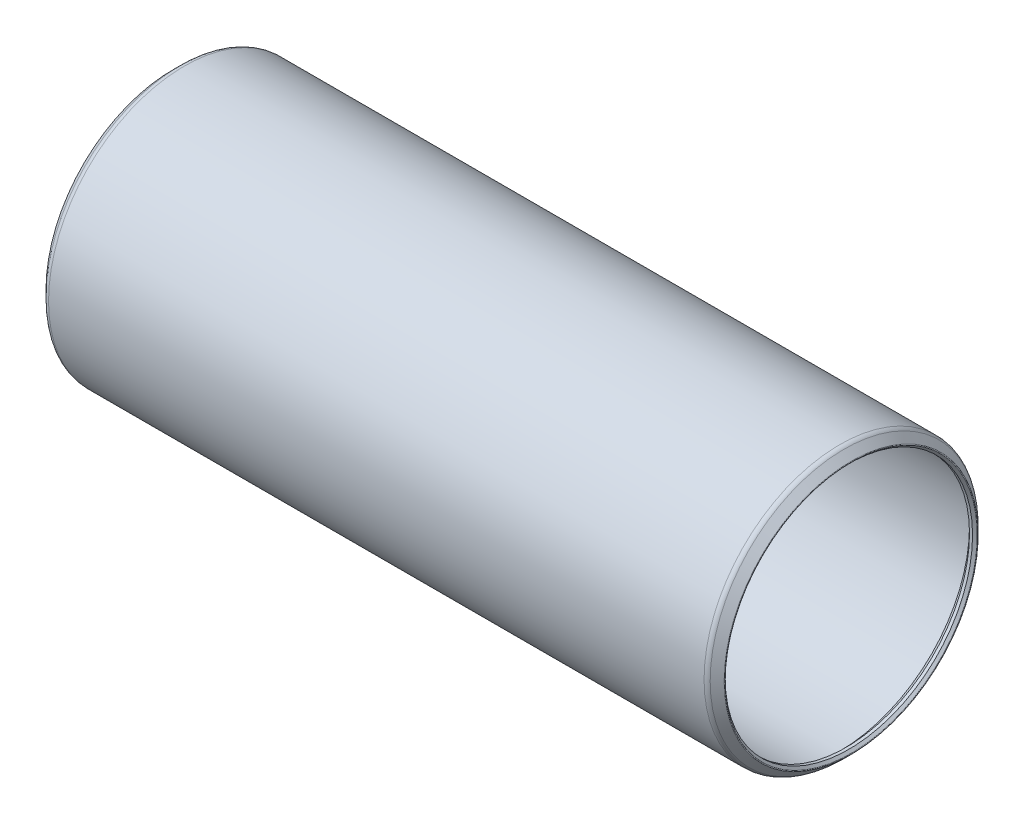
SolidWorks part; units mm, degrees
material "Cast Alloy Steel"
ref_plane "Front Plane" through (0, 0, 0) normal (0, 0, 1) x (1, 0, 0)
ref_plane "Top Plane" through (0, 0, 0) normal (0, 1, 0) x (1, 0, 0)
ref_plane "Right Plane" through (0, 0, 0) normal (1, 0, 0) x (0, 0, -1)
ref_plane "Plane1" through (115.1509, 0, 0) normal (1, 0, 0) x (0, 0, -1)
sketch "Sketch1" plane through (0, 0, 0) normal (0, 0, 1) x (1, 0, 0)
  line L0 (-0.9191, 21.7344) -> (-0.5271, 21.3423)
  line L1 (-0.5271, 21.3423) -> (0, 21.3423)
  line L2 (0, 21.3423) -> (1.0541, 22.3965)
  line L3 (1.0541, 22.3965) -> (114.0968, 22.3965)
  line L4 (114.0968, 22.3965) -> (115.1509, 21.3423)
  line L5 (115.1509, 21.3423) -> (115.6779, 21.3423)
  line L6 (115.6779, 21.3423) -> (116.07, 21.7344)
  line L7 (116.07, 21.914) -> (114.8676, 23.1164)
  line L8 (114.1222, 23.4251) -> (1.0287, 23.4251)
  line L9 (0.2833, 23.1164) -> (-0.9191, 21.914)
  line L10 (115.1509, 0) -> (0, 0) construction
  arc A0 (-0.9191, 21.914) -> (-0.9191, 21.7344) centre (-0.8293, 21.8242) ccw
  arc A1 (116.07, 21.7344) -> (116.07, 21.914) centre (115.9802, 21.8242) ccw
  arc A2 (114.8676, 23.1164) -> (114.1222, 23.4251) centre (114.1222, 22.3711) ccw
  arc A3 (1.0287, 23.4251) -> (0.2833, 23.1164) centre (1.0287, 22.371) ccw
revolve "Revolve1" add sketch "Sketch1" angle 360 about L10 reverse direction yes
ref_plane "Plane2" through (57.5755, 0, 0) normal (1, 0, 0) x (0, 0, -1)
ref_plane "cp1 XY" through (57.5755, 0, 0) normal (1, 0, 0) x (0, 0, -1)
ref_plane "cp1 XZ" through (0, 23.4251, 0) normal (0, -1, 0) x (-1, 0, 0)
ref_plane "cp1 YZ" through (0, 0, 0) normal (0, 0, -1) x (-1, 0, 0)
ref_axis "cp1 X" through (57.5755, 23.4251, 80.9) along (0, 0, -1)
ref_axis "cp1 Y" through (57.5755, -50, 0) along (0, 1, 0)
ref_axis "cp1 Z" through (80.9, 23.4251, 0) along (-1, 0, 0)
sketch3d "cp1"
  point P0 (57.5755, 23.4251, 0)
ref_plane "cp2 XY" through (57.5755, 0, 0) normal (1, 0, 0) x (0, 0, -1)
ref_plane "cp2 XZ" through (0, 0, 0) normal (0, -1, 0) x (-1, 0, 0)
ref_plane "cp2 YZ" through (0, 0, -23.4251) normal (0, 0, -1) x (-1, 0, 0)
ref_axis "cp2 X" through (57.5755, 0, 80.9) along (0, 0, -1)
ref_axis "cp2 Y" through (57.5755, -50, -23.4251) along (0, 1, 0)
ref_axis "cp2 Z" through (80.9, 0, -23.4251) along (-1, 0, 0)
sketch3d "cp2"
  point P0 (57.5755, 0, -23.4251)
ref_plane "cp3 XY" through (57.5755, 0, 0) normal (1, 0, 0) x (0, 0, -1)
ref_plane "cp3 XZ" through (0, -23.4251, 0) normal (0, -1, 0) x (-1, 0, 0)
ref_plane "cp3 YZ" through (0, 0, 0) normal (0, 0, -1) x (-1, 0, 0)
ref_axis "cp3 X" through (57.5755, -23.4251, 80.9) along (0, 0, -1)
ref_axis "cp3 Y" through (57.5755, -50, 0) along (0, 1, 0)
ref_axis "cp3 Z" through (80.9, -23.4251, 0) along (-1, 0, 0)
sketch3d "cp3"
  point P0 (57.5755, -23.4251, 0)
ref_plane "cp4 XY" through (57.5755, 0, 0) normal (1, 0, 0) x (0, 0, -1)
ref_plane "cp4 XZ" through (0, 0, 0) normal (0, -1, 0) x (-1, 0, 0)
ref_plane "cp4 YZ" through (0, 0, 23.4251) normal (0, 0, -1) x (-1, 0, 0)
ref_axis "cp4 X" through (57.5755, 0, 80.9) along (0, 0, -1)
ref_axis "cp4 Y" through (57.5755, -50, 23.4251) along (0, 1, 0)
ref_axis "cp4 Z" through (80.9, 0, 23.4251) along (-1, 0, 0)
sketch3d "cp4"
  point P0 (57.5755, 0, 23.4251)
ref_plane "tube_front XY" through (0, 0, 0) normal (1, 0, 0) x (0, 0, -1)
ref_plane "tube_front XZ" through (0, 0, 0) normal (0, -1, 0) x (-1, 0, 0)
ref_plane "tube_front YZ" through (0, 0, 0) normal (0, 0, -1) x (-1, 0, 0)
ref_axis "tube_front X" through (0, 0, 80.9) along (0, 0, -1)
ref_axis "tube_front Y" through (0, -50, 0) along (0, 1, 0)
ref_axis "tube_front Z" through (80.9, 0, 0) along (-1, 0, 0)
sketch3d "tube_front"
  point P0 (0, 0, 0)
ref_plane "tube_rear XY" through (115.1509, 0, 0) normal (1, 0, 0) x (0, 0, -1)
ref_plane "tube_rear XZ" through (0, 0, 0) normal (0, -1, 0) x (-1, 0, 0)
ref_plane "tube_rear YZ" through (0, 0, 0) normal (0, 0, -1) x (-1, 0, 0)
ref_axis "tube_rear X" through (115.1509, 0, 80.9) along (0, 0, -1)
ref_axis "tube_rear Y" through (115.1509, -50, 0) along (0, 1, 0)
ref_axis "tube_rear Z" through (80.9, 0, 0) along (-1, 0, 0)
sketch3d "tube_rear"
  point P0 (115.1509, 0, 0)
